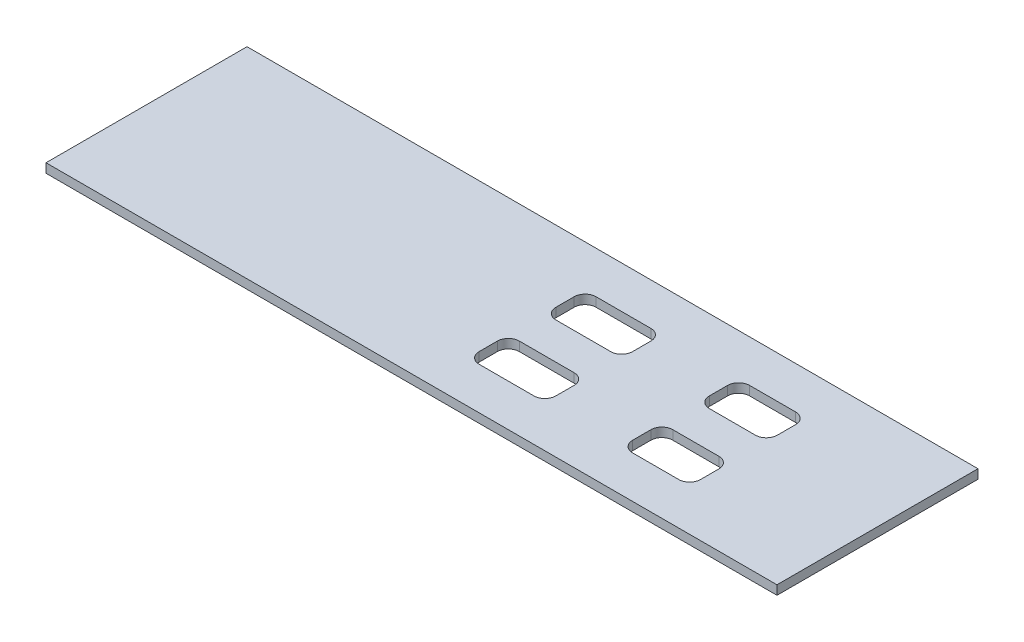
SolidWorks part; units mm, degrees
ref_plane "Front Plane" through (0, 0, 0) normal (0, 0, 1) x (1, 0, 0)
ref_plane "Top Plane" through (0, 0, 0) normal (0, 1, 0) x (1, 0, 0)
ref_plane "Right Plane" through (0, 0, 0) normal (1, 0, 0) x (0, 0, -1)
sketch "Sketch1" plane through (0, 0, 0) normal (0, 1, 0) x (1, 0, 0)
  line L1 (0, 0) -> (152.4, 0)
  line L2 (0, 0) -> (0, 69.85)
  line L3 (0, 69.85) -> (152.4, 69.85)
  line L4 (152.4, 0) -> (152.4, 69.85)
  dimension "D1" = 69.85
  dimension "D2" = 152.4
extrude "Boss-Extrude1" add sketch "Sketch1" along normal blind 3.175
sketch "Sketch2" plane through (0, 3.175, 0) normal (0, 1, 0) x (1, 0, 0)
  line L0 (0, 69.85) -> (0, 0) construction
  line L1 (30.48, 55.245) -> (57.15, 55.245)
  line L2 (30.48, 55.245) -> (30.48, 41.275)
  line L3 (30.48, 41.275) -> (57.15, 41.275)
  line L4 (57.15, 55.245) -> (57.15, 41.275)
  line L5 (83.82, 55.245) -> (107.442, 55.245)
  line L6 (83.82, 55.245) -> (83.82, 41.275)
  line L7 (83.82, 41.275) -> (107.442, 41.275)
  line L8 (107.442, 55.245) -> (107.442, 41.275)
  line L9 (152.4, 0) -> (152.4, 69.85) construction
  line L10 (30.48, 28.575) -> (57.15, 28.575)
  line L11 (30.48, 28.575) -> (30.48, 14.605)
  line L12 (30.48, 14.605) -> (57.15, 14.605)
  line L13 (57.15, 28.575) -> (57.15, 14.605)
  line L14 (83.82, 28.575) -> (107.442, 28.575)
  line L15 (83.82, 28.575) -> (83.82, 14.605)
  line L16 (83.82, 14.605) -> (107.442, 14.605)
  line L17 (107.442, 28.575) -> (107.442, 14.605)
  point P10 (83.82, 48.26)
  point P17 (0, 34.925)
  point P22 (0, 0)
  point P25 (29.21, 34.925)
  point P26 (0, 0)
  point P27 (16.4499, 34.925)
  dimension "D1" = 26.67
  dimension "D2" = 23.622
  dimension "D3" = 44.958
  dimension "D4" = 13.97
  dimension "D5" = 12.7
  dimension "D6" = 6.35
  dimension "D7" = 30.48
extrude "Cut-Extrude1" cut sketch "Sketch2" against normal through all
fillet "Fillet1" radius 3.81 16 edges at (83.82, 1.5875, -14.605) (83.82, 1.5875, -41.275) (30.48, 1.5875, -41.275) (30.48, 1.5875, -14.605) (107.442, 1.5875, -14.605) (57.15, 1.5875, -41.275) (57.15, 1.5875, -14.605) (107.442, 1.5875, -41.275) (107.442, 1.5875, -28.575) (107.442, 1.5875, -55.245) (57.15, 1.5875, -28.575) (57.15, 1.5875, -55.245) (30.48, 1.5875, -28.575) (83.82, 1.5875, -28.575) (83.82, 1.5875, -55.245) (30.48, 1.5875, -55.245)
sketch "Sketch4" plane through (0, 0, 0) normal (-1, 0, 0) x (0, 0, 1)
  line L1 (-69.85, 3.175) -> (0, 3.175)
  line L2 (-69.85, 3.175) -> (-69.85, 0)
  line L3 (-69.85, 0) -> (0, 0)
  line L4 (0, 3.175) -> (0, 0)
extrude "Boss-Extrude2" add sketch "Sketch4" along normal blind 101.6
